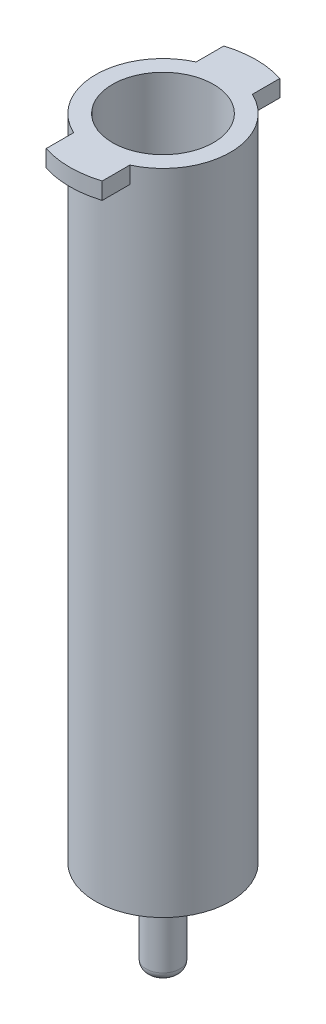
SolidWorks part; units mm, degrees
ref_plane "Front Plane" through (0, 0, 0) normal (0, 0, 1) x (1, 0, 0)
ref_plane "Top Plane" through (0, 0, 0) normal (0, 1, 0) x (1, 0, 0)
ref_plane "Right Plane" through (0, 0, 0) normal (1, 0, 0) x (0, 0, -1)
sketch "Sketch1" plane through (0, 0, 0) normal (0, 1, 0) x (1, 0, 0)
  circle A0 centre (0, 0) radius 6
extrude "Boss-Extrude1" add sketch "Sketch1" along normal blind 58.5
shell "Shell1" thickness 1.5 removed face at (0, 58.5, 6)
sketch "Sketch3" plane through (0, 0, 0) normal (0, -1, 0) x (1, 0, 0)
  circle A0 centre (0, 0) radius 2.5
extrude "Boss-Extrude2" add sketch "Sketch3" along normal blind 1.3
sketch "Sketch4" plane through (0, -1.3, 0) normal (0, -1, 0) x (1, 0, 0)
  circle A0 centre (0, 0) radius 1.5
extrude "Boss-Extrude3" add sketch "Sketch4" along normal blind 6.2
sketch "Sketch5" plane through (0, -7.5, 0) normal (0, -1, 0) x (1, 0, 0)
  circle A0 centre (0, 0) radius 0.7
extrude "Cut-Extrude1" cut sketch "Sketch5" against normal through all
fillet "Fillet1" radius 0.75 1 edges at (0, -7.5, -1.5)
chamfer "Chamfer1" distance 5 angle 8 1 edges at (0, 0, 6) first distance on face at (0, 0, -2.5)
sketch "Sketch6" plane through (0, 58.5, 0) normal (0, 1, 0) x (1, 0, 0)
  line L1 (2.5, 5.4544) -> (2.5, 7.9145)
  line L3 (-2.5, 5.4544) -> (-2.5, 7.9145)
  line L4 (-1.0574, 0) -> (1.504, 0) construction
  line L5 (-2.5, -5.4544) -> (-2.5, -7.9145)
  line L6 (2.5, -5.4544) -> (2.5, -7.9145)
  arc A0 (2.5, 7.9145) -> (-2.5, 7.9145) centre (0, 0) ccw
  arc A1 (-2.5, 5.4544) -> (2.5, 5.4544) centre (0, 0) cw
  arc A3 (2.5, -7.9145) -> (-2.5, -7.9145) centre (0, 0) cw
  arc A4 (-2.5, -5.4544) -> (2.5, -5.4544) centre (0, 0) ccw
extrude "Boss-Extrude4" add sketch "Sketch6" against normal blind 1.5
